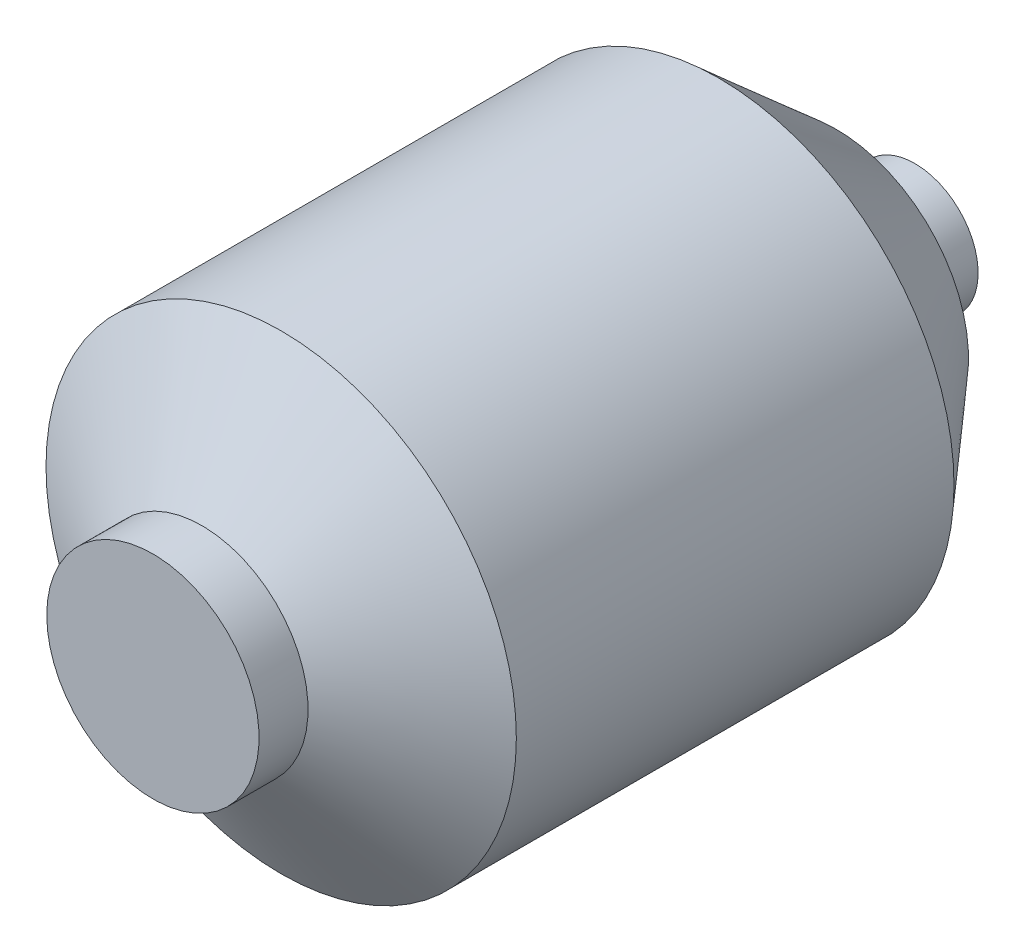
SolidWorks part; units mm, degrees
ref_plane "Front Plane" through (0, 0, 0) normal (0, 0, 1) x (1, 0, 0)
ref_plane "Top Plane" through (0, 0, 0) normal (0, 1, 0) x (1, 0, 0)
ref_plane "Right Plane" through (0, 0, 0) normal (1, 0, 0) x (0, 0, -1)
sketch "Sketch1" plane through (0, 0, 0) normal (0, 1, 0) x (1, 0, 0)
  line L0 (0, 73.0837) -> (0, -80.6494) construction
  line L1 (-40.4819, 44.0509) -> (-72, 8.1169)
  line L2 (-72, 8.1169) -> (-72, -125.8831)
  line L3 (-72, -125.8831) -> (-32.5, -150.1531)
  line L5 (0, -150.1531) -> (0, 68.1169)
  line L6 (0, 68.1169) -> (-19.3735, 68.1169)
  line L7 (-19.3735, 68.1169) -> (-19.3735, 46.8469)
  line L8 (-19.3735, 46.8469) -> (-40.4819, 44.0509)
  line L9 (-32.5, -150.1531) -> (-32.5, -165.1531)
  line L10 (-32.5, -165.1531) -> (0, -165.1531)
  line L11 (0, -165.1531) -> (0, -150.1531)
  dimension "D1" = 20
  dimension "D2" = 197
  dimension "D3" = 15
  dimension "D5" = 32.5
  dimension "D6" = 72
  dimension "D7" = 21.27
revolve "Revolve1" add sketch "Sketch1" angle 360 about L0
